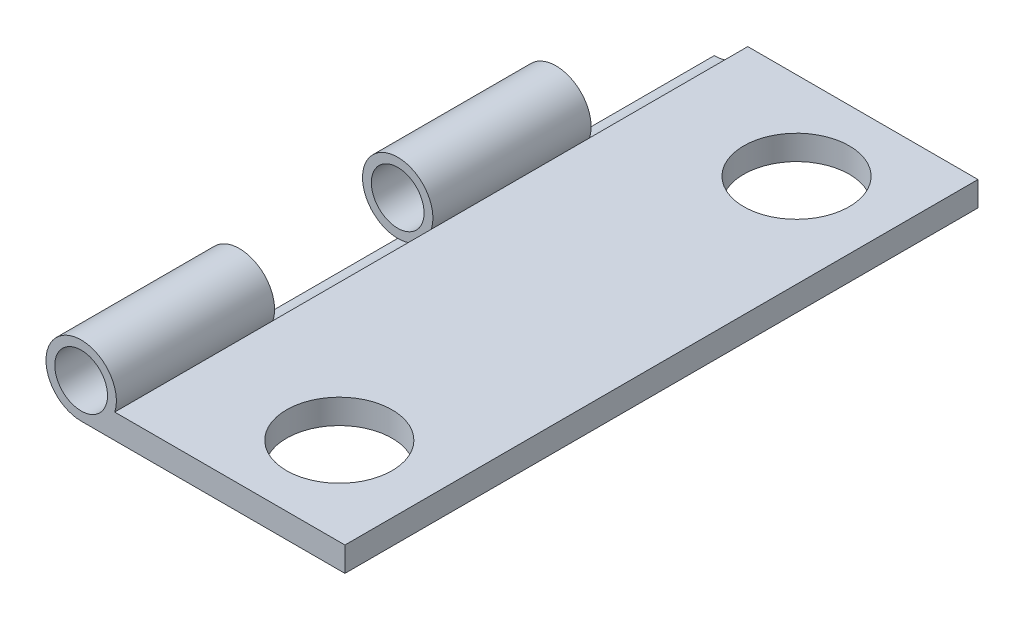
SolidWorks part; units mm, degrees
material "Aluminum Bronze"
ref_plane "Front" through (0, 0, 0) normal (0, 0, 1) x (1, 0, 0)
ref_plane "Top" through (0, 0, 0) normal (0, 1, 0) x (1, 0, 0)
ref_plane "Right" through (0, 0, 0) normal (1, 0, 0) x (0, 0, -1)
sketch "Sketch1" plane through (0, 0, 0) normal (0, 1, 0) x (1, 0, 0)
  line L1 (0, 0) -> (7.5, 0)
  line L2 (0, 0) -> (0, 18)
  line L3 (0, 18) -> (7.5, 18)
  line L4 (7.5, 0) -> (7.5, 18)
  dimension "D1" = 7.5
  dimension "D2" = 18
extrude "Boss-Extrude1" add sketch "Sketch1" along normal blind 0.7
sketch "Sketch2" plane through (0, 0, 0) normal (0, 0, 1) x (1, 0, 0)
  line L0 (0, 0) -> (7.5, 0) construction
  circle A0 centre (0, 1) radius 1
  dimension "D2" = 2
  dimension "D1" = 1
extrude "Boss-Extrude2" add sketch "Sketch2" against normal through all
sketch "Sketch4" plane through (0, 0, 0) normal (0, 0, 1) x (1, 0, 0)
  circle A0 centre (0, 1) radius 0.75
  dimension "D1" = 1.5
extrude "Cut-Extrude1" cut sketch "Sketch4" against normal through all
sketch "Sketch5" plane through (0, 0, 0) normal (0, 0, 1) x (1, 0, 0)
  circle A0 centre (0, 1) radius 1
extrude "Cut-Extrude2" cut sketch "Sketch5" against normal blind 4.5 from offset 4.5 offset against normal yes
pattern_linear "LPattern1" count 2 spacing 9 along (0, 0, -1) of "Cut-Extrude2"
sketch "Sketch6" plane through (0, 0.7, 0) normal (0, 1, 0) x (1, 0, 0)
  line L0 (0.9539, 0) -> (7.5, 0) construction
  line L1 (7.5, 0) -> (7.5, 18) construction
  line L2 (7.5, 9) -> (-1, 9) construction
  circle A0 centre (4.84, 2.5) radius 1.5
  circle A1 centre (4.84, 15.5) radius 1.5
  dimension "D1" = 3
  dimension "D2" = 2.5
  dimension "D3" = 2.66
extrude "Cut-Extrude3" cut sketch "Sketch6" against normal through all
